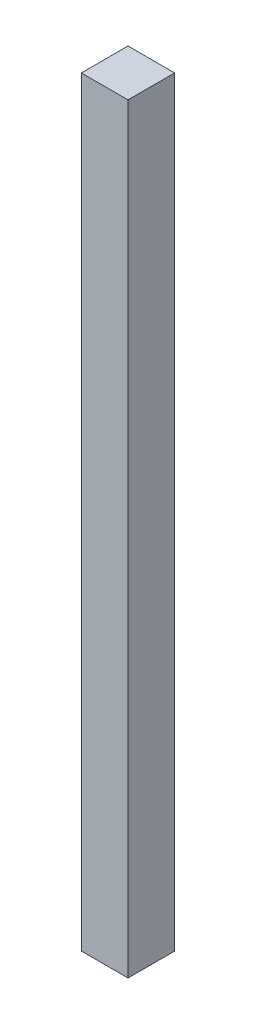
SolidWorks part; units mm, degrees
ref_plane "Plan de face" through (0, 0, 0) normal (0, 0, 1) x (1, 0, 0)
ref_plane "Plan de dessus" through (0, 0, 0) normal (0, 1, 0) x (1, 0, 0)
ref_plane "Plan de droite" through (0, 0, 0) normal (1, 0, 0) x (0, 0, -1)
sketch "Esquisse1" plane through (0, 0, 0) normal (0, 0, 1) x (1, 0, 0)
  line L1 (-81.3222, 77.6389) -> (-71.3222, 77.6389)
  line L2 (-81.3222, 77.6389) -> (-81.3222, -85.3611)
  line L3 (-81.3222, -85.3611) -> (-71.3222, -85.3611)
  line L4 (-71.3222, 77.6389) -> (-71.3222, -85.3611)
  dimension "D1" = 10
  dimension "D2" = 163
extrude "Boss.-Extru.1" add sketch "Esquisse1" along normal blind 10 contours L2 L3 L4 L1
equation "\"EpaisseurPlaque\"= 3"
equation "\"ProfondeurBoite\"=460"
equation "\"LongueurSyphon\"=170"
equation "\"LargeurSyphon\"=120"
equation "\"HauteurCoteDroit\"= 490"
equation "\"HauteurCoteGauche\"= 540"
equation "\"HauteurSolSyphon\"= 300"
equation "\"HauteurSyphon\"=\"HauteurCoteGauche\"-\"HauteurSolSyphon\""
equation "\"LargeurDroite\"=10"
equation "\"LargeurGauche\"=150"
equation "\"LargeurBoite\"= \"LargeurDroite\" + \"LargeurGauche\" + \"LargeurSyphon\""
equation "\"D2@Esquisse1\"=\"LongueurSyphon\" -  10 + 3"
